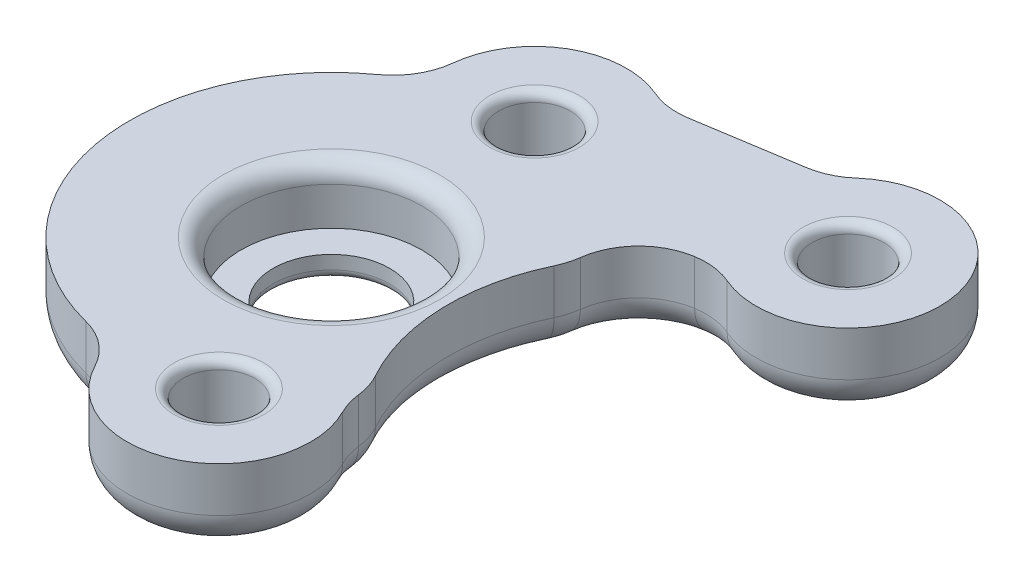
SolidWorks part; units mm, degrees
ref_plane "Front Plane" through (0, 0, 0) normal (0, 0, 1) x (1, 0, 0)
ref_plane "Top Plane" through (0, 0, 0) normal (0, 1, 0) x (1, 0, 0)
ref_plane "Right Plane" through (0, 0, 0) normal (1, 0, 0) x (0, 0, -1)
sketch "Sketch1" plane through (0, 0, 0) normal (0, 1, 0) x (1, 0, 0)
  circle A0 centre (0, 0) radius 9
  circle A1 centre (0, 0) radius 4.025
  dimension "D1" = 18
  dimension "D2" = 8.05
extrude "Boss-Extrude1" add sketch "Sketch1" along normal blind 3.5
sketch "Sketch2" plane through (0, 3.5, 0) normal (0, 1, 0) x (1, 0, 0)
  circle A0 centre (3.3433, -8.356) radius 1.6
  circle A1 centre (0.0612, 8.9998) radius 1.6
  circle A2 centre (3.3433, -8.356) radius 4.1
  circle A3 centre (0.0612, 8.9998) radius 4.1
  dimension "D1" = 2.5
extrude "Boss-Extrude2" add sketch "Sketch2" against normal blind 3.5
sketch "Sketch6" plane through (0, 0, 0) normal (0, -1, 0) x (-1, 0, 0)
  circle A0 centre (-14.2, 0) radius 9
  dimension "D1" = 18
  dimension "D2" = 14.2
extrude "Cut-Extrude2" cut sketch "Sketch6" against normal through all
sketch "Sketch3" plane through (0, 0, 0) normal (0, -1, 0) x (-1, 0, 0)
  circle A0 centre (-0.0612, 8.9998) radius 1.6
  arc A1 (-4.7701, -7.6319) -> (-1.8108, -8.8159) centre (0, 0) ccw construction
  arc A2 (1.5334, 8.8684) -> (-1.6538, 8.8467) centre (0, 0) ccw construction
  circle A4 centre (-3.3433, -8.356) radius 1.6
extrude "Cut-Extrude1" cut sketch "Sketch3" against normal blind 3.5
sketch "Sketch4" plane through (0, 0, 0) normal (0, -1, 0) x (-1, 0, 0)
  line L0 (-0.0612, 8.9998) -> (-12.1263, 10.9048) construction
  line L1 (-2.3537, 12.3989) -> (-8.898, 13.4322)
  line L3 (-5.8131, 6.8708) -> (-9.8338, 7.5057)
  circle A0 centre (-12.1263, 10.9048) radius 1.6
  arc A1 (-8.898, 13.4322) -> (-9.8338, 7.5057) centre (-12.1263, 10.9048) ccw
  arc A2 (-2.3537, 12.3989) -> (-4.047, 8.0388) centre (-0.0612, 8.9998) ccw
  arc A3 (-4.047, 8.0388) -> (-5.8131, 6.8708) centre (0, 0) ccw
  circle A5 centre (-12.1263, 10.9048) radius 4.1 construction
  point P4 (-12.1263, 10.9048)
  point P5 (-12.1263, 10.9048)
  point P8 (-7.2556, 11.7052)
  point P9 (-12.1263, 10.9048)
  point P10 (-8.0263, 10.9048)
  point P13 (-8.0263, 10.9048)
  point P17 (-8.0263, 10.9048)
  dimension "D2" = 3
  dimension "D1" = 2.5
extrude "Boss-Extrude3" add sketch "Sketch4" against normal blind 3.5
sketch "Sketch5" plane through (0, 0, 0) normal (0, -1, 0) x (-1, 0, 0)
  circle A0 centre (0, 0) radius 4.025
  circle A1 centre (0, 0) radius 2.6
  dimension "D1" = 5.2
extrude "Boss-Extrude4" add sketch "Sketch5" against normal blind 1
fillet "Fillet1" radius 3 7 edges at (-3.9373, 1.75, -8.0931) (-0.7102, 1.75, 8.9719) (9.8338, 1.75, -7.5057) (8.898, 1.75, -13.4322) (2.3537, 1.75, -12.3989) (7.1, 1.75, -5.5308) (7.1, 1.75, 5.5308)
fillet "Fillet9" radius 3 2 edges at (5.8131, 1.75, -6.8708) (6.7029, 1.75, 6.0059)
fillet "Fillet5" radius 1.5 16 edges at (-2.0077, 0, -12.5396) (-4.406, 0, -8.2391) (-8.8433, 0, 1.6723) (-1.0932, 0, 9.279) (5.2201, 0, 12.0012) (9.6878, 0, -7.3626) (16.1761, 0, -11.5442) (8.7151, 0, -13.5234) (5.6259, 0, -12.9156) (2.4996, 0, -12.542) (7.1582, 0, -6.4755) (6.238, 0, -4.3017) (5.2046, 0, 0.2865) (6.5641, 0, 4.9054) (6.7966, 0, 5.9989) (8.8438, 0, -7.3493)
fillet "Fillet6" radius 0.4 4 edges at (0, 0, -2.6) (0.0612, 0, -7.3998) (3.3433, 0, 9.956) (12.1263, 0, -12.5048)
fillet "Fillet7" radius 0.8 1 edges at (0, 3.5, 4.025)
fillet "Fillet8" radius 0.4 3 edges at (3.3433, 3.5, 9.956) (12.1263, 3.5, -12.5048) (0.0612, 3.5, -7.3998)
equation "\"D2@Sketch6\"=5.2+\"D1@Sketch6\"/2"
